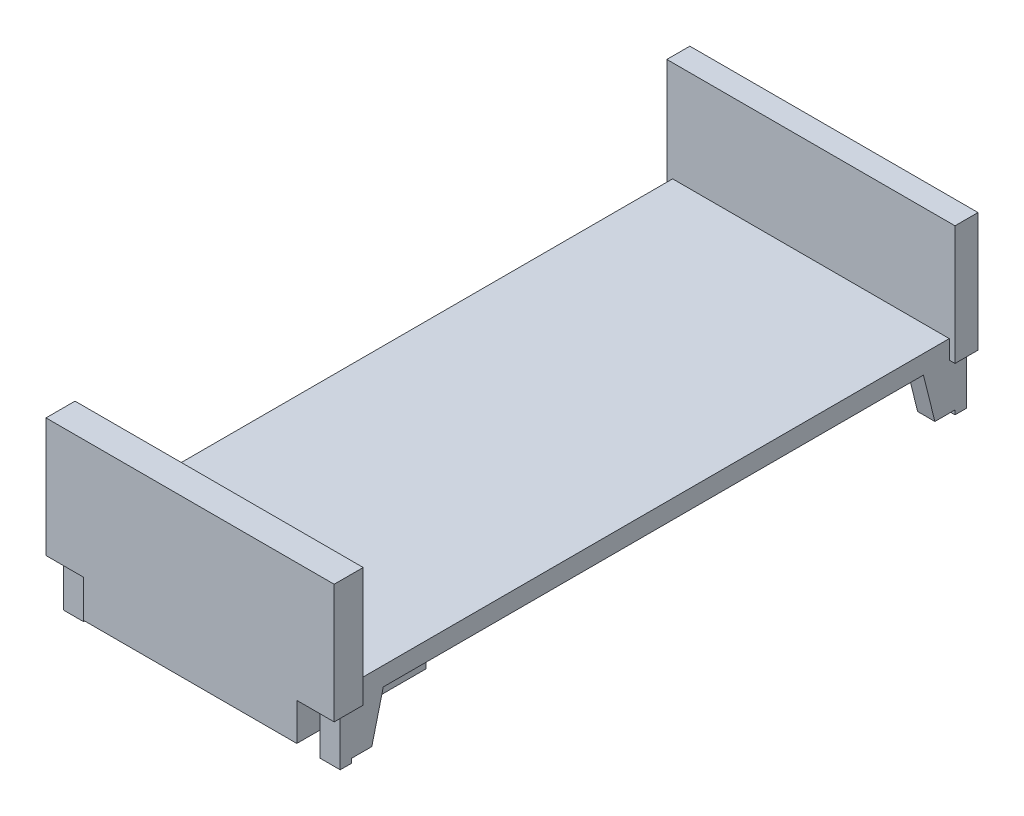
SolidWorks part; units mm, degrees
note: The reader was unsure of these and kept them because the rebuilt part matched: shared geometry of "Sketch1<3>", "Sketch1<4>".
ref_plane "Front Plane" through (0, 0, 0) normal (0, 0, 1) x (1, 0, 0)
ref_plane "Top Plane" through (0, 0, 0) normal (0, 1, 0) x (1, 0, 0)
ref_plane "Right Plane" through (0, 0, 0) normal (1, 0, 0) x (0, 0, -1)
sketch "Sketch1" plane through (0, 0, 0) normal (0, 1, 0) x (1, 0, 0)
  line L0 (-411.5, 40) -> (-451.5, 40)
  line L1 (451.5, 0) -> (-451.5, 0)
  line L2 (451.5, 0) -> (451.5, 2180)
  line L3 (451.5, 2180) -> (-451.5, 2180)
  line L4 (-451.5, 0) -> (-451.5, 2180)
  line L5 (-451.5, 0) -> (451.5, 0)
  line L6 (-451.5, 0) -> (-451.5, 50)
  line L7 (-451.5, 50) -> (451.5, 50)
  line L8 (451.5, 0) -> (451.5, 50)
  line L9 (-451.5, 2180) -> (451.5, 2180)
  line L10 (-451.5, 2180) -> (-451.5, 2130)
  line L11 (-451.5, 2130) -> (451.5, 2130)
  line L12 (451.5, 2180) -> (451.5, 2130)
  line L13 (451.5, 0) -> (411.5, 0)
  line L14 (451.5, 0) -> (451.5, 50)
  line L15 (451.5, 50) -> (411.5, 50)
  line L16 (411.5, 0) -> (411.5, 50)
  line L17 (-451.5, 0) -> (-411.5, 0)
  line L18 (-451.5, 0) -> (-451.5, 50)
  line L19 (-451.5, 50) -> (-411.5, 50)
  line L20 (-411.5, 0) -> (-411.5, 50)
  line L21 (-451.5, 2130) -> (-411.5, 2130)
  line L22 (-451.5, 2130) -> (-451.5, 2180)
  line L23 (-451.5, 2180) -> (-411.5, 2180)
  line L24 (-411.5, 2130) -> (-411.5, 2180)
  line L25 (451.5, 2180) -> (411.5, 2180)
  line L26 (451.5, 2180) -> (451.5, 2130)
  line L27 (451.5, 2130) -> (411.5, 2130)
  line L28 (411.5, 2180) -> (411.5, 2130)
  line L29 (451.5, 40) -> (411.5, 40)
  line L30 (-451.5, 2140) -> (-411.5, 2140)
  line L31 (411.5, 2140) -> (451.5, 2140)
  line L33 (-471.5, 2200) -> (471.5, 2200)
  line L34 (-471.5, 2200) -> (-471.5, 2120)
  line L35 (-471.5, 2120) -> (471.5, 2120)
  line L36 (471.5, 2200) -> (471.5, 2120)
  line L37 (-471.5, 60) -> (471.5, 60)
  line L38 (-471.5, 60) -> (-471.5, -41)
  line L39 (-471.5, -41) -> (471.5, -41)
  line L40 (471.5, 60) -> (471.5, -41)
  dimension "D1" = 2180
  dimension "D2" = 903
  dimension "D3" = 50
  dimension "D4" = 50
  dimension "D5" = 40
  dimension "D6" = 40
  dimension "D7" = 40
  dimension "D8" = 40
  dimension "D9" = 40
  dimension "D10" = 40
  dimension "D11" = 40
  dimension "D12" = 20
  dimension "D13" = 10
  dimension "D14" = 20
  dimension "D15" = 20
  dimension "D16" = 10
  dimension "D17" = 41
  dimension "D18" = 20
  dimension "D19" = 20
extrude "Boss-Extrude1" add sketch "Sketch1" against normal blind 65 contours L4 L37 L2 L35
extrude "Boss-Extrude2" add sketch "Sketch1<3>" against normal blind 50 and the other way blind 350 contours L38 L39 L40 L37 | L33 L36 L35 L34
sketch "Sketch1<3>" plane through (0, 0, 0) normal (0, 1, 0) x (1, 0, 0) same geometry as "Sketch1"
extrude "Boss-Extrude3" add sketch "Sketch1<4>" against normal blind 240 contours L28 L31 L26 L3 | L22 L30 L24 L9 | L1 L20 L0 L4 | L2 L29 L16 L1
sketch "Sketch1<4>" plane through (0, 0, 0) normal (0, 1, 0) x (1, 0, 0) same geometry as "Sketch1"
sketch "Sketch3" plane through (451.5, 0, 0) normal (1, 0, 0) x (0, 0, -1)
  line L0 (60, -65) -> (2120, -65) construction
  line L3 (40, -225) -> (110, -225)
  line L4 (2140, -240) -> (2140, -65) construction
  line L5 (2030, -65) -> (2070, -225)
  line L6 (2070, -225) -> (2140, -225)
  line L7 (110, -225) -> (150, -65)
  line L8 (2140, -240) -> (2140, -65) construction
  line L9 (40, -240) -> (40, -65) construction
  line L10 (40, -225) -> (40, -65)
  line L11 (40, -65) -> (150, -65)
  line L12 (2140, -225) -> (2140, -65)
  line L13 (2140, -65) -> (2030, -65)
  dimension "D1" = 160
  dimension "D2" = 110
  dimension "D3" = 160
  dimension "D4" = 110
  dimension "D5" = 70
  dimension "D6" = 70
extrude "Boss-Extrude4" add sketch "Sketch3" against normal blind 30
sketch "Sketch4" plane through (-451.5, 0, -45.75) normal (1, 0, 0) x (0, 0, -1)
  line L0 (2094.25, -225) -> (2094.25, -65)
  line L2 (2094.25, -240) -> (2094.25, -65) construction
  line L3 (104.25, -65) -> (64.25, -225)
  line L5 (1984.25, -65) -> (2024.25, -225)
  line L6 (2024.25, -225) -> (2094.25, -225)
  line L7 (64.25, -225) -> (-5.75, -225)
  line L8 (2094.25, -65) -> (1984.25, -65)
  line L9 (-5.75, -225) -> (-5.75, -65)
  line L10 (-5.75, -65) -> (104.25, -65)
  line L11 (14.25, -65) -> (2074.25, -65) construction
  line L12 (-5.75, -240) -> (-5.75, -65) construction
  dimension "D1" = 110
  dimension "D2" = 160
  dimension "D3" = 110
  dimension "D4" = 160
  dimension "D5" = 70
  dimension "D6" = 70
extrude "Boss-Extrude5" add sketch "Sketch4" along normal blind 30
sketch "Sketch5" plane through (0, -240, 0) normal (0, -1, 0) x (1, 0, 0)
  line L0 (-431.5, -2180) -> (-431.5, 0)
  line L1 (-416.5, -2175) -> (-446.5, -2175)
  line L2 (-416.5, -2175) -> (-416.5, -2145)
  line L3 (-416.5, -2145) -> (-446.5, -2145)
  line L4 (-446.5, -2175) -> (-446.5, -2145)
  line L5 (416.5, -2175) -> (446.5, -2175)
  line L6 (416.5, -2175) -> (416.5, -2145)
  line L7 (416.5, -2145) -> (446.5, -2145)
  line L8 (446.5, -2175) -> (446.5, -2145)
  line L9 (416.5, -35) -> (446.5, -35)
  line L10 (416.5, -35) -> (416.5, -5)
  line L11 (416.5, -5) -> (446.5, -5)
  line L12 (446.5, -35) -> (446.5, -5)
  line L13 (-446.5, -35) -> (-416.5, -35)
  line L14 (-446.5, -35) -> (-446.5, -5)
  line L15 (-446.5, -5) -> (-416.5, -5)
  line L16 (-416.5, -35) -> (-416.5, -5)
  line L17 (-451.5, -2160) -> (451.5, -2160)
  line L18 (-411.5, 0) -> (-451.5, 0) construction
  line L19 (-451.5, 0) -> (-451.5, -40) construction
  line L20 (451.5, 0) -> (411.5, 0) construction
  line L21 (451.5, 0) -> (451.5, -40) construction
  line L22 (-451.5, -20) -> (451.5, -20)
  line L25 (431.5, 0) -> (431.5, -2180)
  line L27 (451.5, -2180) -> (411.5, -2180) construction
  line L32 (451.5, -2140) -> (451.5, -2180) construction
  line L33 (-451.5, -2140) -> (-451.5, -2180) construction
  line L34 (-411.5, -2180) -> (-451.5, -2180) construction
  point P16 (-446.5, -2160)
  point P29 (-431.5, -5)
  point P36 (-446.5, -20)
  point P43 (431.5, -2175)
  dimension "D1" = 30
extrude "Cut-Extrude1" cut sketch "Sketch5" against normal blind 200 contours L4 L3 L2 L1 | L6 L7 L8 L5 | L10 L11 L12 L9 | L14 L15 L16 L13
sketch "Sketch6" plane through (0, 0, 41) normal (0, 0, 1) x (1, 0, 0)
  line L1 (130, -65) -> (-130, -65)
  line L2 (-471.5, -65) -> (471.5, -65) construction
  arc A0 (-130, -65) -> (130, -65) centre (0, -65) ccw
  dimension "D1" = 130
extrude "Boss-Extrude6" add sketch "Sketch6" against normal blind 30
sketch "Sketch7" plane through (0, 0, -2200) normal (0, 0, -1) x (-1, 0, 0)
  line L1 (130, -65) -> (-130, -65)
  line L2 (471.5, -65) -> (-471.5, -65) construction
  arc A0 (130, -65) -> (-130, -65) centre (0, -65) cw
  dimension "D1" = 130
extrude "Boss-Extrude7" add sketch "Sketch7" against normal blind 30
sketch3d "3DSketch1"
  line L0 (0, -195, 11) -> (0, -155, 11)
  line L1 (0, -155, 11) -> (0, -155, -2170)
  line L2 (0, -155, -2170) -> (0, -195, -2170)
  line L3 (0, -195, -2170) -> (0, -195, 11)
  arc A0 (-130, -65, 11) -> (130, -65, 11) centre (0, -65, 11) ccw construction
  arc A1 (130, -65, -2170) -> (-130, -65, -2170) centre (0, -65, -2170) ccw construction
  point P6 (0, -65, 141)
  point P12 (0, -65, -2300)
  dimension "D1" = 40
extrude "Boss-Extrude8" add sketch "3DSketch1" along a picked direction on the side of the normal blind 20 and the other way blind 20 contours L1 L2 L3 L0
sketch "Sketch8" plane through (0, -65, 0) normal (0, -1, 0) x (1, 0, 0)
  line L0 (130, 41) -> (471.5, 41) construction
  line L1 (-371.5, 41) -> (371.5, 41)
  line L2 (-371.5, 41) -> (-371.5, -409)
  line L3 (-371.5, -409) -> (371.5, -409)
  line L4 (371.5, 41) -> (371.5, -409)
  line L5 (451.5, -150) -> (451.5, -2030) construction
  line L6 (-371.5, -184) -> (-451.5, -184)
  line L7 (-451.5, -150) -> (-451.5, -2030) construction
  line L8 (371.5, -184) -> (451.5, -184)
  dimension "D1" = 80
  dimension "D2" = 450
extrude "Boss-Extrude9" add sketch "Sketch8" along normal blind 130 contours L1 L4 L3 L2
sketch "Sketch12" plane through (-451.5, 0, 0) normal (-1, 0, 0) x (0, 0, 1)
  line L16 (-60, 0) -> (-2120, 0)
  line L17 (-2120, 0) -> (-2120, -65)
  line L18 (-2120, -65) -> (-2180, -65)
  line L19 (-2180, -65) -> (-2180, -240)
  line L20 (-2180, -240) -> (-2140, -240)
  line L21 (-2140, -240) -> (-2140, -225)
  line L22 (-2140, -225) -> (-2070, -225)
  line L23 (-2070, -225) -> (-2030, -65)
  line L24 (-2030, -65) -> (-150, -65)
  line L25 (-150, -65) -> (-110, -225)
  line L26 (-110, -225) -> (-40, -225)
  line L27 (-40, -225) -> (-40, -240)
  line L28 (-40, -240) -> (0, -240)
  line L29 (0, -240) -> (0, -65)
  line L30 (0, -65) -> (-60, -65)
  line L31 (-60, -65) -> (-60, 0)
  line L32 (-60, 0) -> (-2120, 0)
  line L33 (-2120, 0) -> (-2120, -65)
  line L34 (-2120, -65) -> (-2180, -65)
  line L35 (-2180, -65) -> (-2180, -240)
  line L36 (-2180, -240) -> (-2140, -240)
  line L37 (-2140, -240) -> (-2140, -225)
  line L38 (-2140, -225) -> (-2070, -225)
  line L39 (-2070, -225) -> (-2030, -65)
  line L40 (-2030, -65) -> (-150, -65)
  line L41 (-150, -65) -> (-110, -225)
  line L42 (-110, -225) -> (-40, -225)
  line L43 (-40, -225) -> (-40, -240)
  line L44 (-40, -240) -> (0, -240)
  line L45 (0, -240) -> (0, -65)
  line L46 (0, -65) -> (-60, -65)
  line L47 (-60, -65) -> (-60, 0)
  dimension "D1" = 0
extrude "Boss-Extrude14" add sketch "Sketch12" along normal blind 30
sketch "Sketch13" plane through (451.5, 0, 0) normal (1, 0, 0) x (0, 0, -1)
  line L16 (2120, 0) -> (60, 0)
  line L17 (60, 0) -> (60, -65)
  line L18 (60, -65) -> (0, -65)
  line L19 (0, -65) -> (0, -240)
  line L20 (0, -240) -> (40, -240)
  line L21 (40, -240) -> (40, -225)
  line L22 (40, -225) -> (110, -225)
  line L23 (110, -225) -> (150, -65)
  line L24 (150, -65) -> (2030, -65)
  line L25 (2030, -65) -> (2070, -225)
  line L26 (2070, -225) -> (2140, -225)
  line L27 (2140, -225) -> (2140, -240)
  line L28 (2140, -240) -> (2180, -240)
  line L29 (2180, -240) -> (2180, -65)
  line L30 (2180, -65) -> (2120, -65)
  line L31 (2120, -65) -> (2120, 0)
  line L32 (2120, 0) -> (60, 0)
  line L33 (60, 0) -> (60, -65)
  line L34 (60, -65) -> (0, -65)
  line L35 (0, -65) -> (0, -240)
  line L36 (0, -240) -> (40, -240)
  line L37 (40, -240) -> (40, -225)
  line L38 (40, -225) -> (110, -225)
  line L39 (110, -225) -> (150, -65)
  line L40 (150, -65) -> (2030, -65)
  line L41 (2030, -65) -> (2070, -225)
  line L42 (2070, -225) -> (2140, -225)
  line L43 (2140, -225) -> (2140, -240)
  line L44 (2140, -240) -> (2180, -240)
  line L45 (2180, -240) -> (2180, -65)
  line L46 (2180, -65) -> (2120, -65)
  line L47 (2120, -65) -> (2120, 0)
  dimension "D1" = 0
extrude "Boss-Extrude15" add sketch "Sketch13" along normal blind 30
sketch3d "3DSketch2"
  line L0 (471.5, 0, -2200) -> (-471.5, 0, -2200)
  line L1 (471.5, -65, -2200) -> (471.5, 350, -2200) construction
  line L2 (-471.5, -65, -2200) -> (-471.5, 350, -2200) construction
  line L3 (0, 350, -2200) -> (0, 0, -2200)
  line L4 (-471.5, 350, -2200) -> (471.5, 350, -2200) construction
sketch "Sketch14" plane through (-471.5, 0, 0) normal (-1, 0, 0) x (0, 0, 1)
  line L6 (-2120, 350) -> (-2200, 350)
  line L7 (-2200, 350) -> (-2200, -65)
  line L8 (-2200, -65) -> (-2180, -65)
  line L9 (-2180, -65) -> (-2120, -65)
  line L10 (-2120, -65) -> (-2120, 0)
  line L11 (-2120, 0) -> (-2120, 350)
  line L12 (-2120, 350) -> (-2200, 350)
  line L13 (-2200, 350) -> (-2200, -65)
  line L14 (-2200, -65) -> (-2180, -65)
  line L15 (-2180, -65) -> (-2120, -65)
  line L16 (-2120, -65) -> (-2120, 0)
  line L17 (-2120, 0) -> (-2120, 350)
  dimension "D1" = 0
extrude "Boss-Extrude16" add sketch "Sketch14" along normal blind 30
sketch "Sketch15" plane through (-471.5, 0, 0) normal (-1, 0, 0) x (0, 0, 1)
  line L6 (41, -65) -> (41, 350)
  line L7 (41, 350) -> (-60, 350)
  line L8 (-60, 350) -> (-60, 0)
  line L9 (-60, 0) -> (-60, -65)
  line L10 (-60, -65) -> (0, -65)
  line L11 (0, -65) -> (41, -65)
  line L12 (41, -65) -> (41, 350)
  line L13 (41, 350) -> (-60, 350)
  line L14 (-60, 350) -> (-60, 0)
  line L15 (-60, 0) -> (-60, -65)
  line L16 (-60, -65) -> (0, -65)
  line L17 (0, -65) -> (41, -65)
  dimension "D1" = 0
extrude "Boss-Extrude17" add sketch "Sketch15" along normal blind 30
sketch "Sketch16" plane through (471.5, 0, 0) normal (1, 0, 0) x (0, 0, -1)
  line L6 (2200, 350) -> (2120, 350)
  line L7 (2120, 350) -> (2120, 0)
  line L8 (2120, 0) -> (2120, -65)
  line L9 (2120, -65) -> (2180, -65)
  line L10 (2180, -65) -> (2200, -65)
  line L11 (2200, -65) -> (2200, 350)
  line L12 (2200, 350) -> (2120, 350)
  line L13 (2120, 350) -> (2120, 0)
  line L14 (2120, 0) -> (2120, -65)
  line L15 (2120, -65) -> (2180, -65)
  line L16 (2180, -65) -> (2200, -65)
  line L17 (2200, -65) -> (2200, 350)
  dimension "D1" = 0
extrude "Boss-Extrude18" add sketch "Sketch16" along normal blind 30
sketch "Sketch17" plane through (471.5, 0, 0) normal (1, 0, 0) x (0, 0, -1)
  line L6 (60, -65) -> (60, 0)
  line L7 (60, 0) -> (60, 350)
  line L8 (60, 350) -> (-41, 350)
  line L9 (-41, 350) -> (-41, -65)
  line L10 (-41, -65) -> (0, -65)
  line L11 (0, -65) -> (60, -65)
  line L12 (60, -65) -> (60, 0)
  line L13 (60, 0) -> (60, 350)
  line L14 (60, 350) -> (-41, 350)
  line L15 (-41, 350) -> (-41, -65)
  line L16 (-41, -65) -> (0, -65)
  line L17 (0, -65) -> (60, -65)
  dimension "D1" = 0
extrude "Boss-Extrude19" add sketch "Sketch17" along normal blind 30
